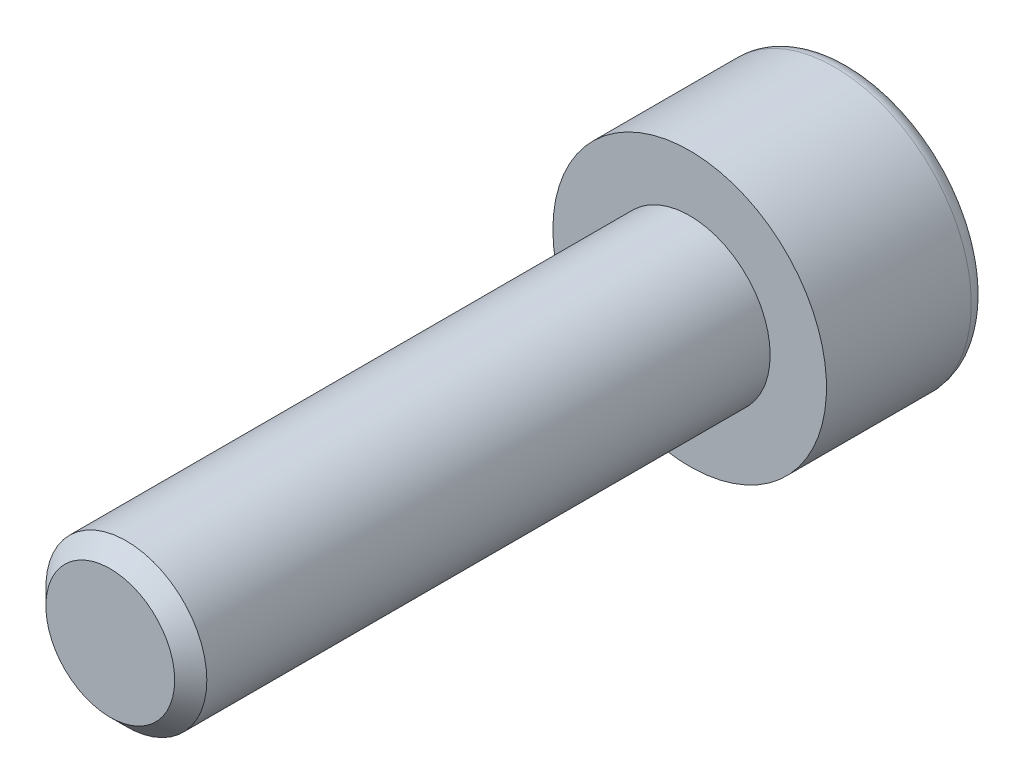
SolidWorks part; units mm, degrees
ref_plane "Plan1" through (0, 0, 0) normal (0, 0, 1) x (1, 0, 0)
ref_plane "Plan2" through (0, 0, 0) normal (0, 1, 0) x (1, 0, 0)
ref_plane "Plan3" through (0, 0, 0) normal (1, 0, 0) x (0, 0, -1)
ref_axis "Z Axis" through (0, 0, -50) along (0, 0, 1)
sketch "Esquisse1" plane through (0, 0, 0) normal (0, 1, 0) x (1, 0, 0)
  line L0 (0, 0) -> (0, 5) construction
  line L1 (0, 0) -> (4.25, 0)
  line L2 (0, 0) -> (0, 5)
  line L3 (0, 5) -> (3.75, 5)
  line L5 (4.25, 0) -> (4.25, 4.5)
  arc A0 (3.75, 5) -> (4.25, 4.5) centre (3.75, 4.5) cw
  dimension "D3" = 0.5
  dimension "D1" = 4.25
  dimension "D2" = 5
revolve "Base-Révolution" add sketch "Esquisse1" angle 360 about L0 reverse direction yes
sketch "Esquisse2" plane through (0, 0, -5) normal (0, 0, 1) x (1, 0, 0)
  line L0 (2, -1.1547) -> (2, 1.1547)
  line L1 (0, 0) -> (2, 1.1547) construction
  line L2 (1, 0) -> (2, 0) construction
  line L3 (0, 2.3094) -> (2, 1.1547)
  line L4 (0, -2.3094) -> (2, -1.1547)
  line L5 (0, 0) -> (0, 2) construction
  line L6 (-2, -1.1547) -> (-2, 1.1547)
  line L7 (0, 2.3094) -> (-2, 1.1547)
  line L8 (0, -2.3094) -> (-2, -1.1547)
  circle A0 centre (0, 0) radius 2 construction
  dimension "D2" = 30
  dimension "D1" = 4
extrude "enlev-mat-Extru1" cut sketch "Esquisse2" along normal blind 2.5
sketch "Esquisse3" plane through (0, 0, 0) normal (0, 1, 0) x (1, 0, 0)
  line L1 (0, 0) -> (0, -18) construction
  line L2 (0, 0) -> (2.5, 0)
  line L3 (0, 0) -> (0, -18)
  line L4 (0, -18) -> (2.5, -18)
  line L6 (2.5, 0) -> (2.5, -18)
  dimension "D1" = 18
  dimension "D2" = 2.5
revolve "Boss.-Révol.1" add sketch "Esquisse3"
cosmetic thread "Représentation de filetage1"
chamfer "Chanfrein1" distance 0.5 angle 45 1 edges at (2.5, 0, 18)
sketch "Esquisse4" plane through (0, 0, 0) normal (0, 1, 0) x (1, 0, 0)
  line L0 (2.012, -18.0488) -> (2.012, -17.9512)
  line L1 (-2.5, -18) -> (2.5, -18) construction
  line L2 (2.012, -17.9512) -> (2.5488, -17.6413)
  line L3 (2.012, -18.0488) -> (2.5488, -18.3587)
  line L4 (2.5488, -17.6413) -> (2.5488, -18.3587)
  line L5 (2.5, -18) -> (2.5, 0) construction
  point P4 (2.5, -18)
  dimension "D2" = 0.0488
  dimension "D3" = 0.0488
  dimension "D4" = 0.5368
  dimension "D5" = 60
  dimension "D1" = 0.488
  dimension "D6" = 60
sketch "Esquisse5" plane through (0, 0, 18) normal (0, 0, 1) x (1, 0, 0)
  circle A0 centre (0, 0) radius 2.5 construction
  circle A1 centre (0, 0) radius 2.5
curve "Hélice1" pitch 0.8 height 16 turns 20
sweep "Enlèvement de matière-Balayage1" [suppressed] cut profiles "Esquisse4" path "Hélice1"
equation "\"D3@Esquisse1\"=\"D2@Esquisse1\"/10"
equation "\"D1@Chanfrein1\"=\"D2@Esquisse3\"*0.2"
equation "\"D3@Esquisse4\"=0.1*\"D1@Esquisse4\""
equation "\"D4@Esquisse4\"=1.1*\"D1@Esquisse4\""
equation "\"D2@Esquisse4\"=0.1*\"D1@Esquisse4\""
equation "\"D1@Esquisse4\"=0.61*\"D4@Hélice1\""
